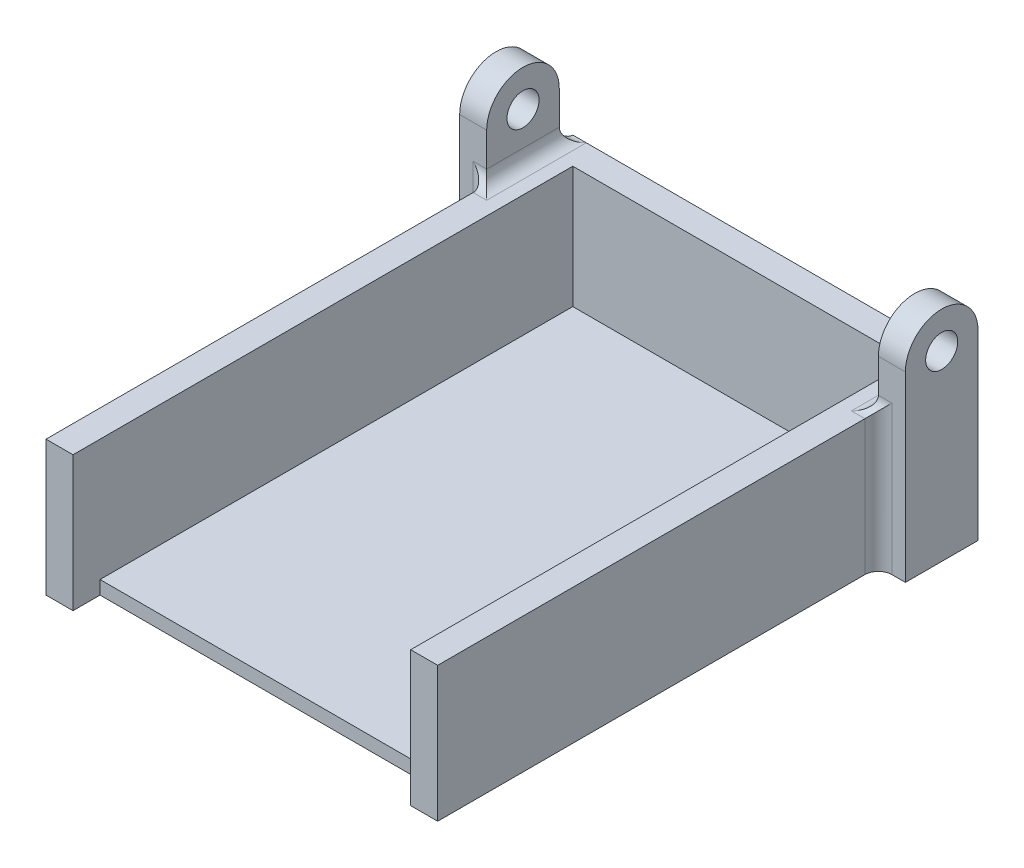
SolidWorks part; units mm, degrees
ref_plane "Front Plane" through (0, 0, 0) normal (0, 0, 1) x (1, 0, 0)
ref_plane "Top Plane" through (0, 0, 0) normal (0, 1, 0) x (1, 0, 0)
ref_plane "Right Plane" through (0, 0, 0) normal (1, 0, 0) x (0, 0, -1)
sketch "Sketch3" plane through (0, 0, 0) normal (0, 1, 0) x (1, 0, 0)
  line L0 (-36.83, 49.53) -> (36.83, 49.53)
  line L1 (-31.75, -44.45) -> (31.75, -44.45)
  line L2 (-31.75, -44.45) -> (-31.75, 44.45)
  line L3 (-31.75, 44.45) -> (31.75, 44.45)
  line L4 (31.75, -44.45) -> (31.75, 44.45)
  line L5 (-31.75, -44.45) -> (31.75, 44.45) construction
  line L6 (-31.75, 44.45) -> (31.75, -44.45) construction
  line L7 (36.83, -49.53) -> (36.83, 49.53)
  line L8 (-36.83, -49.53) -> (36.83, -49.53)
  line L9 (-36.83, -49.53) -> (-36.83, 49.53)
  point P0 (0, 0)
  dimension "D1" = 88.9
  dimension "D2" = 63.5
  dimension "D3" = 5.08
extrude "Boss-Extrude1" add sketch "Sketch3" along normal blind 2.54 contours L1 L4 L3 L2 region at (0, 0, 0)
sketch "Sketch4" plane through (0, 0, 0) normal (0, 1, 0) x (1, 0, 0)
  line L0 (-31.75, -44.45) -> (-31.75, 44.45) construction
  line L1 (-31.75, 44.45) -> (31.75, 44.45) construction
  line L2 (31.75, -44.45) -> (31.75, 44.45) construction
  line L3 (36.83, -49.53) -> (36.83, 49.53) construction
  line L4 (-36.83, 49.53) -> (36.83, 49.53) construction
  line L5 (-36.83, -49.53) -> (-36.83, 49.53) construction
  line L6 (-31.75, -44.45) -> (-31.75, 44.45)
  line L7 (-31.75, 44.45) -> (31.75, 44.45)
  line L8 (31.75, -44.45) -> (31.75, 44.45)
  line L9 (36.83, -49.53) -> (36.83, 49.53)
  line L10 (-36.83, 49.53) -> (36.83, 49.53)
  line L11 (-36.83, -49.53) -> (-36.83, 49.53)
  line L12 (-31.75, -44.45) -> (-31.75, -49.53)
  line L13 (-36.83, -49.53) -> (36.83, -49.53) construction
  line L14 (-31.75, -49.53) -> (-36.83, -49.53)
  line L15 (31.75, -44.45) -> (31.75, -49.53)
  line L16 (31.75, -49.53) -> (36.83, -49.53)
extrude "Boss-Extrude2" add sketch "Sketch4" along normal blind 25.4
sketch "Sketch5" plane through (-36.83, 0, 0) normal (-1, 0, 0) x (0, 0, 1)
  line L0 (-46.99, 34.29) -> (-46.99, 0)
  line L1 (-49.53, 0) -> (49.53, 0) construction
  line L2 (-46.99, 0) -> (-33.3375, 0)
  line L3 (-33.3375, 0) -> (-33.3375, 34.29)
  line L4 (-49.53, 25.4) -> (-49.53, 0) construction
  line L5 (44.45, 2.54) -> (-44.45, 2.54) construction
  line L6 (44.45, 2.54) -> (-44.45, 2.54) construction
  line L7 (44.45, 2.54) -> (44.45, 21.59) construction
  line L8 (44.45, 21.59) -> (-44.45, 21.59) construction
  line L9 (-44.45, 2.54) -> (-44.45, 21.59) construction
  line L10 (44.45, 2.54) -> (-44.45, 21.59) construction
  line L11 (44.45, 21.59) -> (-44.45, 2.54) construction
  line L12 (44.45, 2.54) -> (-44.45, 2.54) construction
  line L13 (-44.45, 25.4) -> (-44.45, 2.54) construction
  line L14 (29.6862, 34.29) -> (-40.1638, 34.29) construction
  line L15 (-40.1638, 34.29) -> (27.0383, 53.34) construction
  line L16 (-40.1638, 34.29) -> (28.8682, 44.9491) construction
  circle A0 centre (-40.1638, 34.29) radius 3.0163
  arc A1 (-46.99, 34.29) -> (-33.3375, 34.29) centre (-40.1638, 34.29) cw
  circle A2 centre (27.0383, 53.34) radius 31.75 construction
  circle A3 centre (29.6862, 34.29) radius 31.75 construction
  circle A4 centre (28.8682, 44.9491) radius 31.75 construction
  point P12 (0, 12.065)
  dimension "D1" = 6.0325
  dimension "D3" = 3.81
  dimension "D6" = 63.5
  dimension "D2" = 2.54
  dimension "D4" = 88.9
  dimension "D5" = 19.05
  dimension "D7" = 12.7
  dimension "D8" = 69.85
extrude "Boss-Extrude3" add sketch "Sketch5" along normal blind 5.08
mirror "Mirror1" about plane through (0, 0, 0) normal (1, 0, 0) of "Boss-Extrude3"
fillet "Fillet1" radius 2.54 4 edges at (36.83, 12.7, -46.99) (36.83, 12.7, -33.3375) (-36.83, 12.7, -46.99) (-36.83, 12.7, -33.3375)
fillet "Fillet2" radius 2.54 6 edges at (38.1, 25.4, -33.3375) (36.83, 25.4, -40.1638) (38.1, 25.4, -46.99) (-38.1, 25.4, -46.99) (-36.83, 25.4, -40.1638) (-38.1, 25.4, -33.3375)
